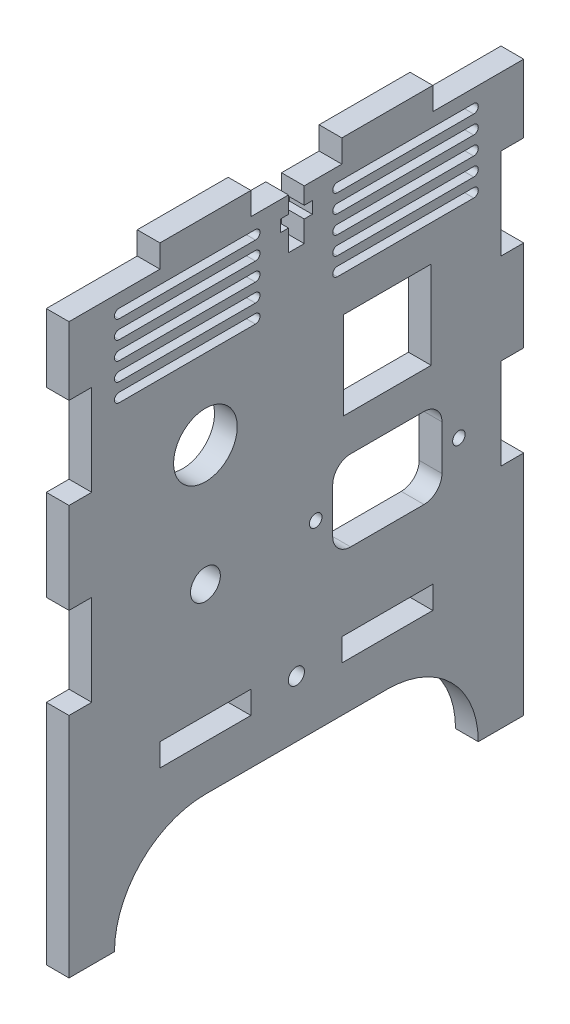
SolidWorks part; units mm, degrees
ref_plane "Front Plane" through (0, 0, 0) normal (0, 0, 1) x (1, 0, 0)
ref_plane "Top Plane" through (0, 0, 0) normal (0, 1, 0) x (1, 0, 0)
ref_plane "Right Plane" through (0, 0, 0) normal (1, 0, 0) x (0, 0, -1)
sketch "Sketch1" plane through (0, 0, 0) normal (1, 0, 0) x (0, 0, -1)
  line L1 (-63.5, 82.55) -> (63.5, 82.55)
  line L2 (-63.5, 82.55) -> (-63.5, -82.55)
  line L3 (-63.5, -82.55) -> (63.5, -82.55)
  line L4 (63.5, 82.55) -> (63.5, -82.55)
  line L5 (-63.5, 82.55) -> (63.5, -82.55) construction
  line L6 (-63.5, -82.55) -> (63.5, 82.55) construction
  point P0 (0, 0)
  dimension "D1" = 127
  dimension "D2" = 165.1
extrude "Boss-Extrude1" add sketch "Sketch1" along normal blind 6.35
sketch "Sketch2" plane through (6.35, 0, 0) normal (1, 0, 0) x (0, 0, -1)
  line L1 (-63.5, 82.55) -> (-38.1, 82.55)
  line L2 (-63.5, 82.55) -> (-63.5, 76.2)
  line L3 (-63.5, 76.2) -> (-38.1, 76.2)
  line L4 (-38.1, 82.55) -> (-38.1, 76.2)
  dimension "D1" = 25.4
  dimension "D2" = 6.35
extrude "Cut-Extrude1" cut sketch "Sketch2" against normal blind 6.35
pattern_linear "LPattern1" count 3 spacing 50.8 along (0, 0, -1) of "Cut-Extrude1"
sketch "Sketch5" plane through (6.35, 0, 0) normal (1, 0, 0) x (0, 0, -1)
  line L0 (-25.4, -82.55) -> (25.4, -82.55) construction
  line L1 (-63.5, -82.55) -> (63.5, -82.55) construction
  line L2 (-25.4, -57.15) -> (25.4, -57.15)
  line L3 (-25.4, -107.95) -> (25.4, -107.95)
  arc A0 (-25.4, -57.15) -> (-25.4, -107.95) centre (-25.4, -82.55) ccw
  arc A1 (25.4, -107.95) -> (25.4, -57.15) centre (25.4, -82.55) ccw
  point P4 (0, -82.55)
  dimension "D2" = 25.4
  dimension "D1" = 50.8
extrude "Cut-Extrude4" cut sketch "Sketch5" against normal blind 6.35
sketch "Sketch8" plane through (6.35, 0, 0) normal (1, 0, 0) x (0, 0, -1)
  line L0 (63.5, -82.55) -> (63.5, 76.2) construction
  line L1 (63.5, 57.15) -> (57.15, 57.15)
  line L2 (63.5, 57.15) -> (63.5, 31.75)
  line L3 (63.5, 31.75) -> (57.15, 31.75)
  line L4 (57.15, 57.15) -> (57.15, 31.75)
  line L5 (38.1, 82.55) -> (12.7, 82.55) construction
  dimension "D1" = 25.4
  dimension "D2" = 25.4
  dimension "D3" = 6.35
extrude "Cut-Extrude6" cut sketch "Sketch8" against normal blind 6.35
pattern_linear "LPattern4" count 2 spacing 50.8 along (0, -1, 0) of "Cut-Extrude6"
ref_plane "Plane1" through (0, 0, 0) normal (0, 0, 1) x (1, 0, 0)
mirror "Mirror1" about plane through (0, 0, 0) normal (0, 0, 1) of "LPattern4"
sketch "Sketch9" plane through (0, 0, 0) normal (-1, 0, 0) x (0, 0, 1)
  line L0 (-63.5, -82.55) -> (-63.5, -19.05) construction
  line L1 (-38.1, -38.1) -> (-12.7, -38.1)
  line L2 (-38.1, -38.1) -> (-38.1, -44.45)
  line L3 (-38.1, -44.45) -> (-12.7, -44.45)
  line L4 (-12.7, -38.1) -> (-12.7, -44.45)
  line L5 (-38.1, 82.55) -> (-12.7, 82.55) construction
  point P6 (-25.4, 82.55)
  dimension "D1" = 25.4
  dimension "D2" = 6.35
  dimension "D3" = 25.4
  dimension "D4" = 120.65
extrude "Cut-Extrude7" cut sketch "Sketch9" against normal blind 6.35
pattern_linear "LPattern6" count 2 spacing 50.8 along (0, 0, 1) of "Cut-Extrude7"
sketch "Sketch16" plane through (0, 0, 0) normal (-1, 0, 0) x (0, 0, 1)
  line L0 (12.7, 76.2) -> (-12.7, 76.2) construction
  line L1 (-2.1971, 76.2) -> (2.1971, 76.2)
  line L2 (-2.1971, 76.2) -> (-2.1971, 62.23)
  line L3 (-2.1971, 62.23) -> (2.1971, 62.23)
  line L4 (2.1971, 76.2) -> (2.1971, 62.23)
  line L5 (-12.7, 76.2) -> (-12.7, 82.55) construction
  line L7 (-4.445, 71.501) -> (4.445, 71.501)
  line L8 (-4.445, 71.501) -> (-4.445, 68.199)
  line L9 (-4.445, 68.199) -> (4.445, 68.199)
  line L10 (4.445, 71.501) -> (4.445, 68.199)
  point P6 (0, 62.23)
  point P13 (0, 71.501)
  point P14 (4.445, 69.85)
  dimension "D1" = 4.3942
  dimension "D2" = 13.97
  dimension "D3" = 12.7
  dimension "D4" = 3.302
  dimension "D5" = 8.89
  dimension "D6" = 12.7
  dimension "D7" = 6.35
extrude "Cut-Extrude14" cut sketch "Sketch16" against normal blind 6.35 contours L7 L10 L9 L8 | L1 L4 L3 L2
hole_wizard "#8 Clearance Hole1" positions "Sketch18" profile "Sketch17" hole size "#8" standard "ANSI Inch"
sketch "Sketch18" plane through (0, 0, 0) normal (-1, 0, 0) x (0, 0, 1)
  line L3 (-12.7, -44.45) -> (-12.7, -38.1) construction
  line L4 (38.1, -38.1) -> (12.7, -38.1) construction
  point P0 (0, -41.275)
  point P16 (-12.7, -41.275)
  dimension "D1" = 12.7
  dimension "D2" = 3.175
sketch "Sketch17" plane through (0, -41.275, 0) normal (0, 1, 0) x (0, 0, 1)
  line L0 (0, 0) -> (0, 11.5107)
  line L1 (0, 11.5107) -> (2.2479, 10.16)
  line L2 (2.2479, 10.16) -> (2.2479, 0)
  line L5 (2.2479, 0) -> (0, 0)
  line L10 (0, 11.5107) -> (-2.2479, 10.16) construction
  line L11 (0, -6.35) -> (0, 107.95) construction
  dimension "Hole Dia." = 4.4958
  dimension "Hole Depth" = 10.16
  dimension "Drill Angle" = 118
sketch "Sketch19" plane through (0, 0, 0) normal (-1, 0, 0) x (0, 0, 1)
  line L0 (-49.53, 71.1789) -> (-11.43, 71.1789) construction
  line L1 (-49.53, 72.4489) -> (-11.43, 72.4489)
  line L2 (-49.53, 69.9089) -> (-11.43, 69.9089)
  line L3 (-38.1, 82.55) -> (-38.1, 76.2) construction
  arc A0 (-49.53, 72.4489) -> (-49.53, 69.9089) centre (-49.53, 71.1789) ccw
  arc A1 (-11.43, 69.9089) -> (-11.43, 72.4489) centre (-11.43, 71.1789) ccw
  point P2 (-30.48, 71.1789)
  point P7 (-30.48, 72.4489)
  dimension "D2" = 1.27
  dimension "D1" = 38.1
  dimension "D3" = 7.62
extrude "Cut-Extrude15" cut sketch "Sketch19" against normal blind 6.35
mirror "Mirror2" about plane through (0, 0, 0) normal (0, 0, 1) of "Cut-Extrude15"
pattern_linear "LPattern7" count 5 spacing 5.08 along (0, -1, 0) of "Mirror2"
sketch "Sketch20" plane through (0, 0, 0) normal (-1, 0, 0) x (0, 0, 1)
  line L1 (-35.65, 4.9) -> (-15.15, 4.9)
  line L2 (-40.65, -0.1) -> (-40.65, -12.6)
  line L3 (-35.65, -17.6) -> (-15.15, -17.6)
  line L4 (-10.15, -0.1) -> (-10.15, -12.6)
  line L5 (-63.5, 6.35) -> (-63.5, 31.75) construction
  circle A0 centre (-45.4, -6.35) radius 1.75
  circle A1 centre (-5.4, -6.35) radius 1.75
  arc A2 (-40.65, -12.6) -> (-35.65, -17.6) centre (-35.65, -12.6) ccw
  arc A3 (-15.15, 4.9) -> (-10.15, -0.1) centre (-15.15, -0.1) cw
  arc A4 (-15.15, -17.6) -> (-10.15, -12.6) centre (-15.15, -12.6) ccw
  arc A5 (-40.65, -0.1) -> (-35.65, 4.9) centre (-35.65, -0.1) cw
  point P8 (-25.4, 4.9)
  point P13 (-40.65, -6.35)
  point P18 (-10.15, 4.9)
  point P21 (-10.15, -17.6)
  point P24 (-40.65, 4.9)
  dimension "D1" = 3.5
  dimension "D2" = 3.5
  dimension "D10" = 5
  dimension "D11" = 5
  dimension "D12" = 5
  dimension "D13" = 5
  dimension "D3" = 40
  dimension "D4" = 30.5
  dimension "D5" = 22.5
  dimension "D6" = 38.1
extrude "Cut-Extrude16" cut sketch "Sketch20" against normal blind 7.62
sketch "Sketch22" plane through (0, 0, 0) normal (-1, 0, 0) x (0, 0, 1)
  line L0 (-15.15, 4.9) -> (-35.65, 4.9) construction
  line L1 (-37.65, 39.56) -> (-13.15, 39.56)
  line L2 (-37.65, 39.56) -> (-37.65, 15.06)
  line L3 (-37.65, 15.06) -> (-13.15, 15.06)
  line L4 (-13.15, 39.56) -> (-13.15, 15.06)
  point P4 (-25.4, 15.06)
  point P5 (-25.4, 4.9)
  dimension "D1" = 24.5
  dimension "D2" = 24.5
  dimension "D3" = 0
  dimension "D4" = 10.16
extrude "Cut-Extrude17" cut sketch "Sketch22" against normal blind 6.35
sketch "Sketch23" plane through (0, 0, 0) normal (-1, 0, 0) x (0, 0, 1)
  line L0 (-13.15, 15.06) -> (-13.15, 39.56) construction
  line L2 (63.5, 31.75) -> (63.5, 6.35) construction
  circle A0 centre (25.4, 27.31) radius 8.89
  point P2 (-13.15, 27.31)
  dimension "D1" = 17.78
  dimension "D2" = 0
  dimension "D3" = 38.1
extrude "Cut-Extrude18" cut sketch "Sketch23" against normal blind 7.62
sketch "Sketch24" plane through (0, 0, 0) normal (-1, 0, 0) x (0, 0, 1)
  line L1 (57.15, 6.35) -> (57.15, -19.05) construction
  circle A0 centre (25.4, -6.35) radius 4.1672
  circle A1 centre (25.4, 27.31) radius 8.89 construction
  point P4 (57.15, -6.35)
  dimension "D1" = 0
  dimension "D2" = 8.3344
  dimension "D3" = 0
extrude "Cut-Extrude19" cut sketch "Sketch24" against normal blind 7.62
